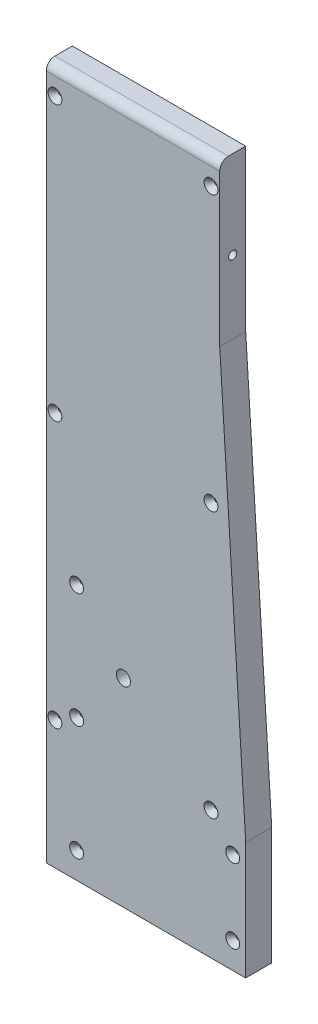
SolidWorks part; units mm, degrees
material "MDF"
ref_plane "Front Plane" through (0, 0, 0) normal (0, 0, 1) x (1, 0, 0)
ref_plane "Top Plane" through (0, 0, 0) normal (0, 1, 0) x (1, 0, 0)
ref_plane "Right Plane" through (0, 0, 0) normal (1, 0, 0) x (0, 0, -1)
sketch "Sketch1" plane through (0, 0, 0) normal (0, 0, 1) x (1, 0, 0)
  line L0 (82.0395, -5024.8784) -> (82.0395, -5533.4155)
  line L1 (82.0395, -5024.8784) -> (82.0395, -5464.9635) construction
  line L8 (-209.0395, -5024.8784) -> (-209.0395, -5142.5528)
  line L11 (-228.0888, -5533.4155) -> (228.0888, -5533.4155)
  line L14 (209.0395, -5142.5528) -> (209.0395, -5024.8784)
  line L15 (209.0395, -5024.8784) -> (-209.0395, -5024.8784)
  line L22 (209.0395, -5142.5528) -> (209.0395, -5024.8784)
  line L23 (209.0395, -5024.8784) -> (82.0395, -5024.8784)
  line L106 (82.0395, -5533.4155) -> (228.0888, -5533.4155)
  line L119 (-209.0395, -5142.5528) -> (-228.0888, -5447.3417)
  line L120 (-228.0888, -5447.3417) -> (-228.0888, -5533.4155)
  line L121 (228.0888, -5533.4155) -> (228.0888, -5447.3417)
  line L122 (228.0888, -5533.4155) -> (228.0888, -5447.3417)
  line L123 (228.0888, -5447.3417) -> (209.0395, -5142.5528)
  line L124 (228.0888, -5447.3417) -> (209.0395, -5142.5528)
  dimension "D1" = 0
extrude "Boss-Extrude1" add sketch "Sketch1" along normal blind 19.05
hole_wizard "3/8 Clearance Hole1" positions "Sketch2" profile "Sketch4" hole size "3/8" standard "ANSI Inch" end condition through all
sketch "Sketch2" plane through (0, 0, 19.05) normal (0, 0, 1) x (1, 0, 0)
  point P9 (138.551, -5387.9638)
sketch "Sketch4" plane through (138.551, -5387.9638, 19.05) normal (1, 0, 0) x (0, -1, 0)
  line L0 (0, 0) -> (0, 19.05)
  line L1 (0, 19.05) -> (5.1587, 19.05)
  line L2 (5.1587, 19.05) -> (5.1587, 0)
  line L5 (5.1587, 0) -> (0, 0)
  line L11 (0, -6.35) -> (0, 107.95) construction
  dimension "Thru Hole Dia." = 10.3175
  dimension "Thru Hole Depth" = 19.05
hole_wizard "Hole1" positions "Sketch5" profile "Sketch6" legacy
sketch "Sketch5" plane through (0, -5562.8703, 19.05) normal (0, 0, 1) x (1, 0, 0)
  line L0 (218.5638, 29.4548) -> (218.5638, 115.5175) construction
  line L4 (202.6895, 537.9919) -> (202.6895, 97.9067) construction
  line L9 (88.3895, 537.9919) -> (88.3895, 97.9067) construction
  line L13 (104.2638, 29.4548) -> (104.2638, 235.8996) construction
  line L16 (0, 537.9919) -> (0, 29.4548) construction
  point P0 (218.5638, 102.8175)
  point P2 (218.5638, 48.5048)
  point P33 (202.6895, 123.3067)
  point P35 (202.6895, 317.9493)
  point P37 (202.6895, 518.9419)
  point P51 (88.3895, 518.9419)
  point P53 (88.3895, 317.9493)
  point P55 (88.3895, 123.3067)
  point P69 (104.2638, 216.8496)
  point P71 (104.2638, 132.6772)
  point P73 (104.2638, 48.5048)
  point P83 (-104.2638, 48.5048)
  point P84 (-104.2638, 132.6772)
  point P85 (-104.2638, 216.8496)
  point P86 (-88.3895, 123.3067)
  point P87 (-88.3895, 317.9493)
  point P88 (-88.3895, 518.9419)
  point P89 (-202.6895, 518.9419)
  point P90 (-202.6895, 317.9493)
  point P91 (-202.6895, 123.3067)
  point P92 (-218.5638, 48.5048)
  point P93 (-218.5638, 102.8175)
sketch "Sketch6" plane through (218.5638, -5460.0528, 19.05) normal (1, 0, 0) x (0, -1, 0)
  line L0 (0, 0) -> (0, 51.7539)
  line L1 (0, 51.7539) -> (1.5875, 50.8)
  line L2 (1.5875, 50.8) -> (1.5875, 4.0177)
  line L3 (1.5875, 4.0177) -> (5.08, 0)
  line L4 (5.08, 0) -> (0, 0)
  line L5 (0, -14.3089) -> (0, 102.4216) construction
  line L6 (0, 51.7539) -> (-1.5875, 50.8) construction
  line L7 (-1.5875, 4.0177) -> (-5.08, 0) construction
  dimension "Diameter" = 3.175
  dimension "Depth" = 50.8
  dimension "C-Sink Diameter" = 10.16
  dimension "C-Sink Angle" = 82
  dimension "Drill Angle" = 118
hole_wizard "15/64 (0.23438) Diameter Hole1" positions "Sketch7" profile "Sketch9" hole size "15/64" standard "ANSI Inch"
sketch "Sketch7" plane through (209.0395, 0, 0) normal (1, 0, 0) x (0, 0, -1)
  point P0 (-9.5266, -5089.2261)
sketch "Sketch9" plane through (209.0395, -5089.2261, 9.5266) normal (0, 1, 0) x (0, 0, -1)
  line L0 (0, 0) -> (0, 25.4)
  line L1 (0, 25.4) -> (2.9766, 23.6115)
  line L2 (2.9766, 23.6115) -> (2.9766, 0)
  line L5 (2.9766, 0) -> (0, 0)
  line L10 (0, 25.4) -> (-2.9766, 23.6115) construction
  line L11 (0, -6.35) -> (0, 107.95) construction
  dimension "Hole Dia." = 5.9533
  dimension "Hole Depth" = 25.4
  dimension "Drill Angle" = 118
fillet "Fillet1" radius 6.35 1 edges at (145.5395, -5024.8784, 19.05)
